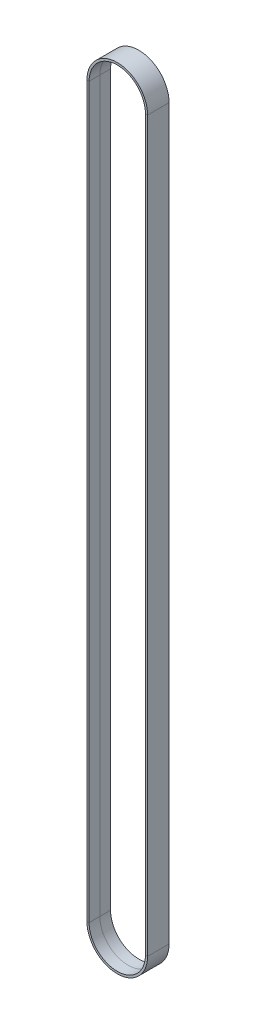
SolidWorks part; units mm, degrees
ref_plane "Спереди" through (0, 0, 0) normal (0, 0, 1) x (1, 0, 0)
ref_plane "Сверху" through (0, 0, 0) normal (0, 1, 0) x (1, 0, 0)
ref_plane "Справа" through (0, 0, 0) normal (1, 0, 0) x (0, 0, -1)
sketch "Эскиз2" plane through (0, 0, 0) normal (0, 0, 1) x (1, 0, 0)
  line L0 (0, 0) -> (1, 0) construction
  line L1 (0, 0) -> (0, 1) construction
  line L2 (26.25, 0) -> (26.25, -678.6787)
  line L3 (-26.25, -678.6787) -> (-26.25, 0)
  arc A0 (-26.25, 0) -> (26.25, 0) centre (0, 0) cw
  arc A1 (26.25, -678.6787) -> (-26.25, -678.6787) centre (0, -678.6787) cw
ref_plane "Плоскость1" through (0, 0, 0) normal (0, 0, 1) x (1, 0, 0)
sketch "Эскиз3" plane through (0, 0, 0) normal (0, 0, 1) x (1, 0, 0)
  line L0 (-26.25, -678.6787) -> (-26.25, 0) construction
  line L1 (26.25, 0) -> (26.25, -678.6787) construction
  line L2 (-26.25, -678.6787) -> (-26.25, 0)
  line L3 (26.25, 0) -> (26.25, -678.6787)
  arc A0 (-26.25, -678.6787) -> (26.25, -678.6787) centre (0, -678.6787) ccw construction
  arc A1 (26.25, 0) -> (-26.25, 0) centre (0, 0) ccw construction
  arc A2 (-26.25, -678.6787) -> (26.25, -678.6787) centre (0, -678.6787) ccw
  arc A3 (26.25, 0) -> (-26.25, 0) centre (0, 0) ccw
ref_plane "Плоскость2" through (0, 0, 0) normal (0, 1, 0) x (1, 0, 0)
sketch "Эскиз4" plane through (0, 0, 0) normal (0, 1, 0) x (1, 0, 0)
  line L0 (19.0352, -10) -> (17.3233, -10) construction
  line L2 (26.25, 0) -> (26.25, -10)
  line L3 (26.25, -10) -> (28.25, -10)
  line L5 (17.3233, 10) -> (19.0352, 10) construction
  line L7 (26.25, 0) -> (26.25, 10)
  line L8 (26.25, 10) -> (28.25, 10)
  line L10 (28.25, 10) -> (28.25, -10)
  dimension "D1" = 2
  dimension "D2" = 2
sweep "По траектории1" add profiles "Эскиз4" path "Эскиз3"
